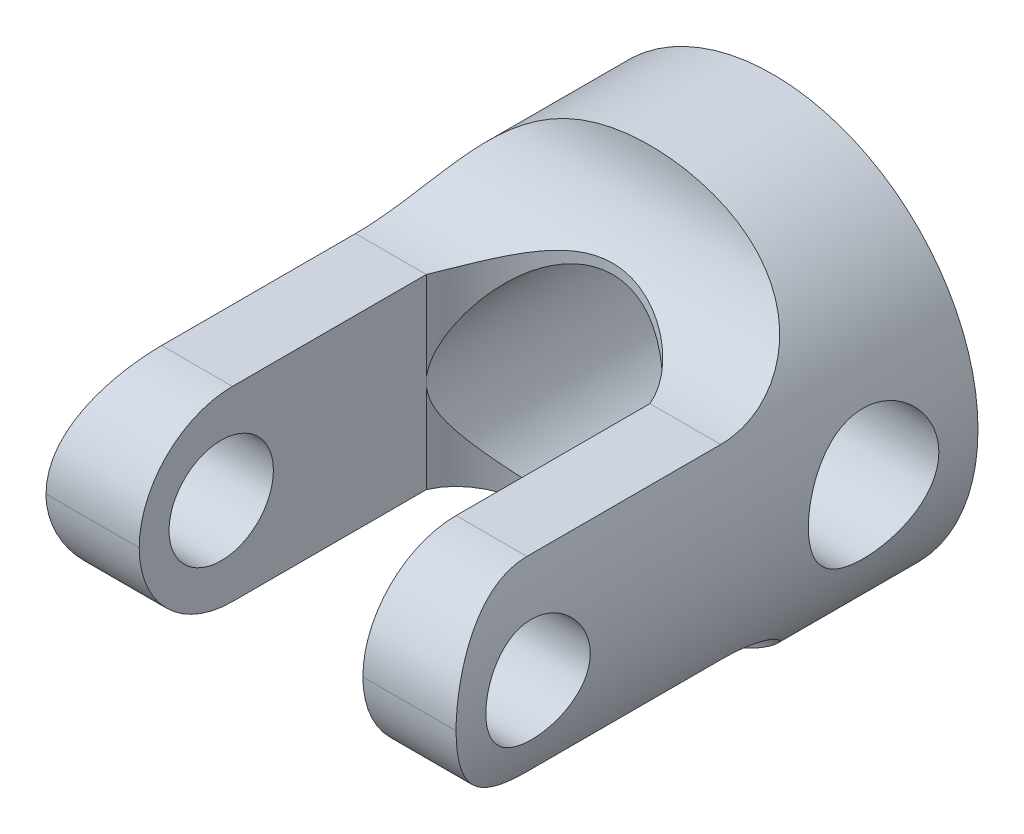
SolidWorks part; units mm, degrees
ref_plane "前视基准面" through (0, 0, 0) normal (0, 0, 1) x (1, 0, 0)
ref_plane "上视基准面" through (0, 0, 0) normal (0, 1, 0) x (1, 0, 0)
ref_plane "右视基准面" through (0, 0, 0) normal (1, 0, 0) x (0, 0, -1)
sketch "草图1" plane through (0, 0, 0) normal (0, 0, 1) x (1, 0, 0)
  circle A0 centre (0, 0) radius 5.5
  dimension "D1" = 11
extrude "凸台-拉伸1" add sketch "草图1" along normal blind 14
sketch "草图2" plane through (0, 0, 0) normal (0, 0, -1) x (-1, 0, 0)
  circle A0 centre (0, 0) radius 3
  dimension "D1" = 6
extrude "切除-拉伸1" cut sketch "草图2" against normal through all
sketch "草图3" plane through (0, 0, 0) normal (0, 1, 0) x (1, 0, 0)
  line L0 (0, 1.9765) -> (0, -15.1997) construction
  line L1 (-3, -14) -> (3, -14)
  line L2 (-5.5, -14) -> (5.5, -14) construction
  line L3 (3, -14) -> (3, -6.3)
  line L4 (5.5, 0) -> (-5.5, 0) construction
  line L5 (-3, -14) -> (-3, -6.3)
  line L6 (3, 0) -> (-3, 0) construction
  arc A0 (-3, -6.3) -> (3, -6.3) centre (0, -7.55) cw
  point P11 (0, -14)
  point P13 (0, -4.3)
  dimension "D3" = 4.3
  dimension "D1" = 6
  dimension "D2" = 6.3
extrude "切除-拉伸2" cut sketch "草图3" against normal through all both and the other way through all
sketch "草图4" plane through (0, 0, 0) normal (1, 0, 0) x (0, 0, -1)
  line L0 (-15.3139, 0) -> (1.6227, 0) construction
  line L1 (-14, 2.5) -> (-6.3, 2.5)
  line L2 (-14, 4.6098) -> (-14, -4.6098) construction
  line L4 (0, -5.5) -> (0, 5.5) construction
  line L5 (-14, -2.5) -> (-6.3, -2.5)
  line L8 (-3.345, 8.923) -> (-14, 8.923)
  line L9 (-14, 8.923) -> (-14, 2.5)
  line L11 (-6.5388, -8.0437) -> (-14, -8.0437)
  line L12 (-14, -8.0437) -> (-14, -2.5)
  line L13 (-6.5388, -8.0437) -> (-3.7602, -7.0967)
  line L14 (-3.345, 6.0174) -> (-3.345, 8.923)
  arc A0 (-6.3, 2.5) -> (-3.345, 6.0174) centre (-6.3, 5.5) ccw
  arc A1 (-6.3, -2.5) -> (-3.7602, -7.0967) centre (-6.3, -5.5) cw
  point P10 (-2.5048, 8.923)
  point P13 (-14, 0)
  point P20 (-2.5048, 7.0175)
  point P21 (-6.8561, -7.4693)
  point P23 (-4.0776, -6.5223)
  dimension "D3" = 3
  dimension "D4" = 3
  dimension "D1" = 5
  dimension "D2" = 6.3
extrude "切除-拉伸3" cut sketch "草图4" against normal through all both and the other way through all
fillet "圆角1" radius 2.5 4 edges at (-3.9495, -2.5, 14) (-3.9495, 2.5, 14) (3.9495, 2.5, 14) (3.9495, -2.5, 14)
sketch "草图5" plane through (0, 0, 0) normal (1, 0, 0) x (0, 0, -1)
  line L0 (1.7771, 0) -> (-16.7188, 0) construction
  circle A0 centre (-2.8, 0) radius 1.75
  dimension "D1" = 2.8
  dimension "D2" = 3.5
extrude "切除-拉伸4" cut sketch "草图5" along normal through all
sketch "草图6" plane through (0, 0, 0) normal (1, 0, 0) x (0, 0, -1)
  line L0 (1.8079, 0) -> (-15.7771, 0) construction
  circle A0 centre (-11.8, 0) radius 1.4
  dimension "D1" = 2.2
  dimension "D2" = 2.8
extrude "切除-拉伸5" cut sketch "草图6" against normal through all both and the other way through all
